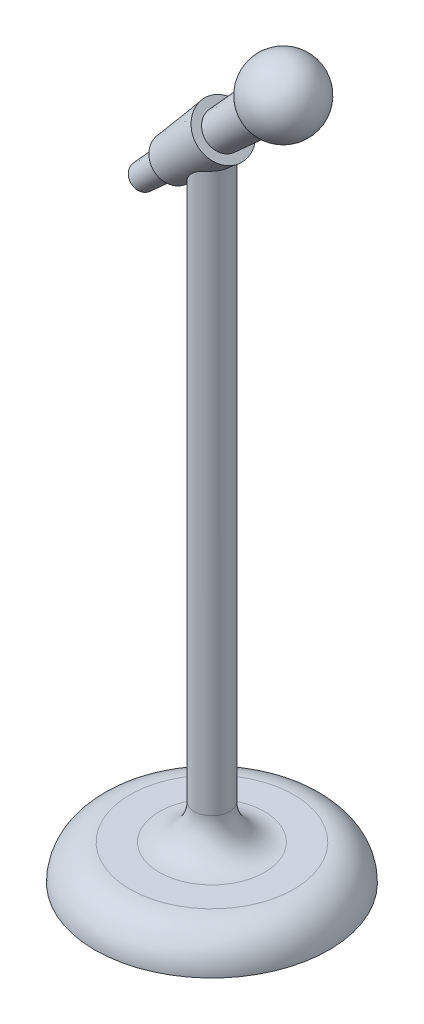
SolidWorks part; units mm, degrees
ref_plane "Front Plane" through (0, 0, 0) normal (0, 0, 1) x (1, 0, 0)
ref_plane "Top Plane" through (0, 0, 0) normal (0, 1, 0) x (1, 0, 0)
ref_plane "Right Plane" through (0, 0, 0) normal (1, 0, 0) x (0, 0, -1)
sketch "Sketch1" plane through (0, 0, 0) normal (0, 0, 1) x (1, 0, 0)
  line L0 (0, 110) -> (-3, 110)
  line L1 (0, -55) -> (0, 55) construction
  line L2 (-3, 110) -> (-3, 6)
  line L3 (-3, 6) -> (-20, 6)
  line L4 (-20, 6) -> (-20, 0)
  line L5 (55, 0) -> (-55, 0) construction
  line L6 (-20, 0) -> (0, 0)
  line L7 (0, 0) -> (0, 110)
  line L8 (0, 110) -> (0, 49.9984) construction
  dimension "D1" = 6
  dimension "D2" = 6
  dimension "D3" = 110
  dimension "D4" = 20
revolve "Revolve1" add sketch "Sketch1" angle 360 about L8
fillet "Fillet1" radius 6 1 edges at (0, 6, 3)
sketch "Sketch2" plane through (0, 0, 0) normal (0, 0, 1) x (1, 0, 0)
  line L0 (-11.852, 98.5442) -> (16.4322, 126.8285) construction
  line L1 (3, 110) -> (-3, 110) construction
  line L3 (-11.852, 98.5442) -> (-13.2662, 99.9584)
  line L4 (-13.2662, 99.9584) -> (6.2633, 121.6482)
  line L6 (-11.852, 98.5442) -> (16.4322, 126.8285)
  line L7 (16.4322, 126.8285) -> (22.8153, 120.4454) construction
  arc A0 (16.4322, 126.8285) -> (6.2633, 121.6482) centre (12.1896, 122.5858) ccw
  point P1 (-13.6721, 102.1557)
  point P5 (-12.1118, 103.0918)
  point P6 (-11.852, 98.5442)
  dimension "D4" = 6
  dimension "D1" = 45
  dimension "D2" = 40
  dimension "D3" = 3
  dimension "D5" = 2
revolve "Revolve2" add sketch "Sketch2" angle 360 about L0
sketch "Sketch3" plane through (43.3461, 43.3461, 0) normal (-0.7071, -0.7071, 0) x (0, 0, 1)
  circle A2 centre (0, 78.0619) radius 4.5
  circle A3 centre (0, 78.0619) radius 4.5
  dimension "D1" = 2.5
extrude "Boss-Extrude1" add sketch "Sketch3" along normal blind 12 draft 5 from offset 19.5 offset against normal yes
fillet "Fillet2" radius 6 1 edges at (0, 6, 20)
